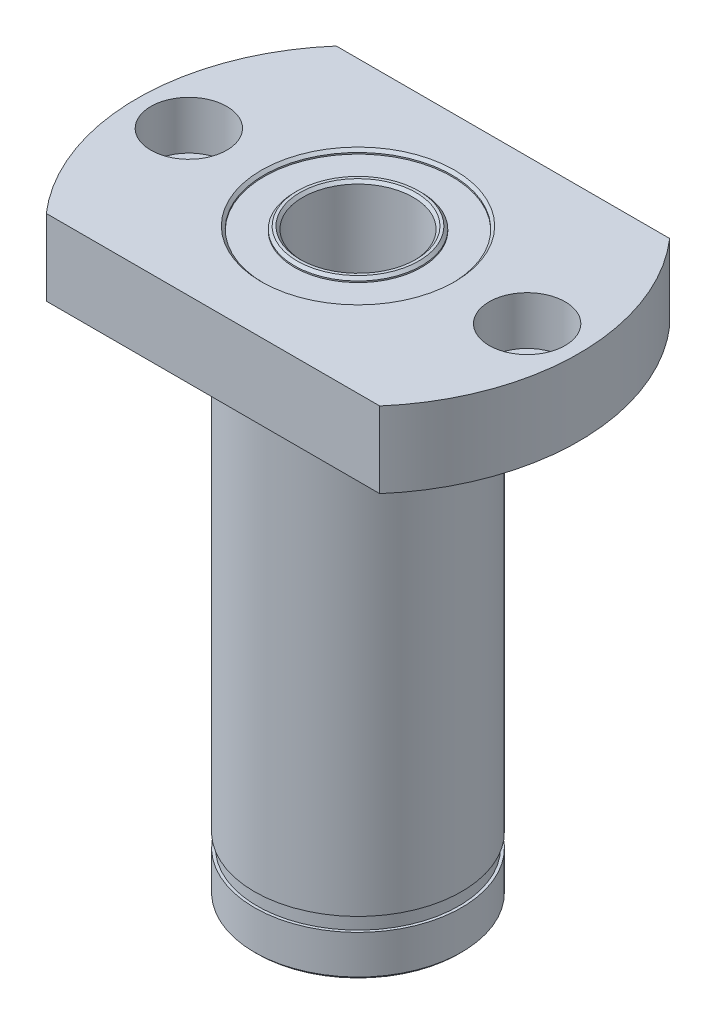
SolidWorks part; units mm, degrees
ref_plane "Front Plane" through (0, 0, 0) normal (0, 0, 1) x (1, 0, 0)
ref_plane "Top Plane" through (0, 0, 0) normal (0, 1, 0) x (1, 0, 0)
ref_plane "Right Plane" through (0, 0, 0) normal (1, 0, 0) x (0, 0, -1)
sketch "Sketch1" plane through (0, 0, 0) normal (0, 1, 0) x (1, 0, 0)
  circle A0 centre (0, 0) radius 7.5
  dimension "D1" = 15
extrude "Extrude1" add sketch "Sketch1" along normal blind 36.5
sketch "Sketch2" plane through (0, 36.5, 0) normal (0, 1, 0) x (1, 0, 0)
  line L1 (-16, 10.5) -> (16, 10.5)
  line L2 (-16, 10.5) -> (-16, -10.5)
  line L3 (-16, -10.5) -> (16, -10.5)
  line L4 (16, 10.5) -> (16, -10.5)
  dimension "D1" = 10.5
  dimension "D2" = 16
  dimension "D3" = 32
  dimension "D4" = 21
extrude "Extrude2" add sketch "Sketch2" along normal blind 5.5
sketch "Sketch3" plane through (0, 0, 0) normal (0, -1, 0) x (1, 0, 0)
  circle A0 centre (0, 0) radius 4
  dimension "D1" = 8
extrude "Extrude3" cut sketch "Sketch3" against normal blind 42
sketch "Sketch4" plane through (0, 42, 0) normal (0, 1, 0) x (1, 0, 0)
  circle A0 centre (0, 0) radius 16
  circle A1 centre (0, 0) radius 21
  dimension "D1" = 32
  dimension "D2" = 5
extrude "Extrude4" cut sketch "Sketch4" against normal blind 10
sketch "Sketch5" plane through (0, 0, 0) normal (0, -1, 0) x (1, 0, 0)
  circle A0 centre (0, 0) radius 6.8
  circle A1 centre (0, 0) radius 4.6
  dimension "D1" = 9.2
  dimension "D2" = 13.6
extrude "Extrude5" cut sketch "Sketch5" against normal blind 0.3
sketch "Sketch6" plane through (0, 42, 0) normal (0, 1, 0) x (1, 0, 0)
  circle A0 centre (0, 0) radius 6.8
  circle A1 centre (0, 0) radius 4.6
  dimension "D1" = 9.2
  dimension "D2" = 13.6
extrude "Extrude6" cut sketch "Sketch6" against normal blind 0.3
sketch "Sketch7" plane through (0, 0, 0) normal (1, 0, 0) x (0, 0, -1)
  line L0 (7.5, 0) -> (7.5, 36.5) construction
  line L1 (7.5, 4) -> (7.3, 4)
  line L2 (7.5, 4) -> (7.5, 3)
  line L3 (7.5, 3) -> (7.3, 3)
  line L4 (7.3, 4) -> (7.3, 3)
  line L5 (0, 0) -> (0, 5) construction
  dimension "D1" = 3
  dimension "D2" = 1
  dimension "D3" = 0.2
  dimension "D4" = 5
revolve "Cut-Revolve1" cut sketch "Sketch7" angle 360 about L5
sketch "Sketch8" plane through (0, 42, 0) normal (0, 1, 0) x (1, 0, 0)
  line L0 (-12.25, 0) -> (12.25, 0) construction
  circle A0 centre (-12.25, 0) radius 2.75
  circle A1 centre (12.25, 0) radius 2.75
  circle A2 centre (-12.25, 0) radius 1.5
  circle A3 centre (12.25, 0) radius 1.5
  dimension "D3" = 5.5
  dimension "D4" = 5.5
  dimension "D5" = 3
  dimension "D6" = 3
  dimension "D1" = 24.5
  dimension "D2" = 12.25
extrude "Extrude7" cut sketch "Sketch8" against normal blind 8 contours A2 | A3
extrude "Extrude8" cut sketch "Sketch8<3>" against normal blind 3.5 contours A1 | A0
sketch "Sketch8<3>" plane through (0, 42, 0) normal (0, 1, 0) x (1, 0, 0) same geometry as "Sketch8"
chamfer "Chamfer1" distance 0.2 angle 45 7 edges at (0, 0, -4) (0, 0, 7.5) (0, 0, -4.6) (0, 0, -6.8) (0, 42, 4.6) (0, 42, -4) (0, 42, 6.8)
